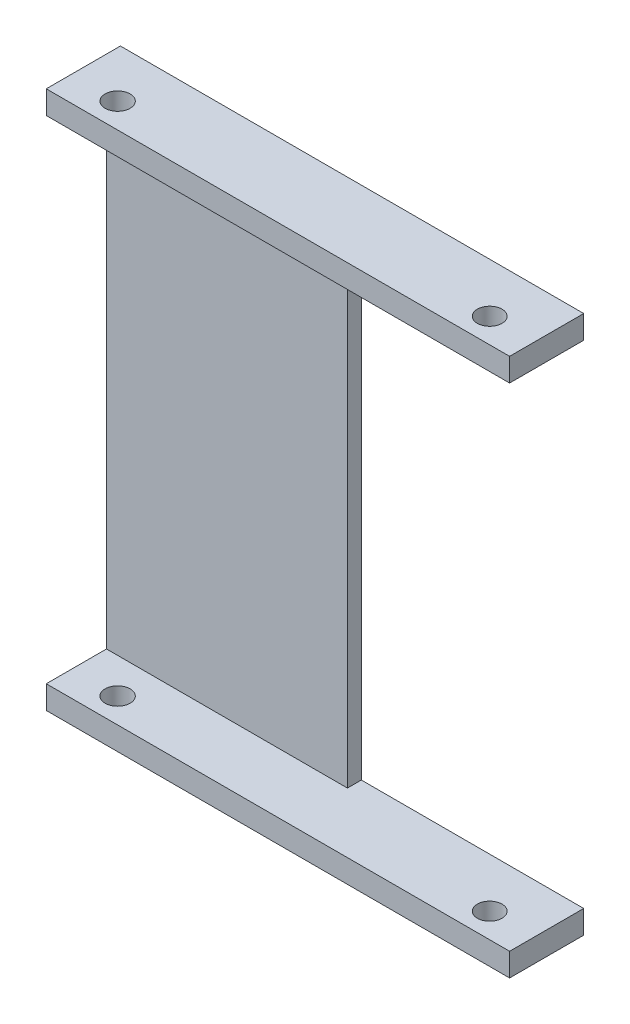
SolidWorks part; units mm, degrees
ref_plane "Front Plane" through (0, 0, 0) normal (0, 0, 1) x (1, 0, 0)
ref_plane "Top Plane" through (0, 0, 0) normal (0, 1, 0) x (1, 0, 0)
ref_plane "Right Plane" through (0, 0, 0) normal (1, 0, 0) x (0, 0, -1)
sketch "Sketch1" plane through (0, 0, 0) normal (0, 0, 1) x (1, 0, 0)
  line L1 (0, 0) -> (127, 0)
  line L2 (0, 0) -> (0, 147.574)
  line L3 (0, 147.574) -> (127, 147.574)
  line L4 (127, 0) -> (127, 147.574)
  dimension "D1" = 127
  dimension "D2" = 147.574
extrude "Boss-Extrude1" add sketch "Sketch1" along normal blind 3.81
sketch "Sketch3" plane through (0, 0, 3.81) normal (0, 0, 1) x (1, 0, 0)
  line L0 (127, 0) -> (127, 147.574) construction
  line L1 (0, 147.574) -> (127, 147.574)
  line L2 (0, 147.574) -> (0, 141.224)
  line L3 (0, 141.224) -> (127, 141.224)
  line L4 (127, 147.574) -> (127, 141.224)
  line L6 (0, 0) -> (127, 0)
  line L7 (0, 0) -> (0, 6.35)
  line L8 (0, 6.35) -> (127, 6.35)
  line L9 (127, 0) -> (127, 6.35)
  dimension "D1" = 6.35
  dimension "D2" = 6.35
extrude "Boss-Extrude2" add sketch "Sketch3" along normal blind 16.51
sketch "Sketch4" plane through (0, 0, 0) normal (0, -1, 0) x (1, 0, 0)
  line L0 (0, 20.32) -> (127, 20.32) construction
  line L1 (0, 20.32) -> (0, 0) construction
  circle A0 centre (12.7, 13.462) radius 3.429
  circle A3 centre (114.7608, 13.5387) radius 3.3782 construction
  circle A4 centre (114.7608, 13.5387) radius 3.3782
  dimension "D3" = 6.858
  dimension "D6" = 6.858
  dimension "D1" = 12.7
extrude "Cut-Extrude1" cut sketch "Sketch4" against normal through all
sketch "Sketch7" plane through (0, 0, 3.81) normal (0, 0, 1) x (1, 0, 0)
  line L0 (127, 73.787) -> (66.04, 73.787) construction
  line L1 (127, 6.35) -> (127, 141.224) construction
  line L2 (66.04, 141.224) -> (66.04, 6.35) construction
  line L3 (0, 141.224) -> (127, 141.224) construction
  line L4 (127, 6.35) -> (0, 6.35) construction
  line L6 (127, 141.224) -> (66.04, 141.224)
  line L7 (127, 141.224) -> (127, 6.35)
  line L8 (127, 6.35) -> (66.04, 6.35)
  line L9 (66.04, 141.224) -> (66.04, 6.35)
  dimension "D1" = 60.96
extrude "Cut-Extrude3" cut sketch "Sketch7" against normal up to surface (3.81 mm away) contours L7 L6 L9 L8 up to face at (63.5, 73.787, 0)
